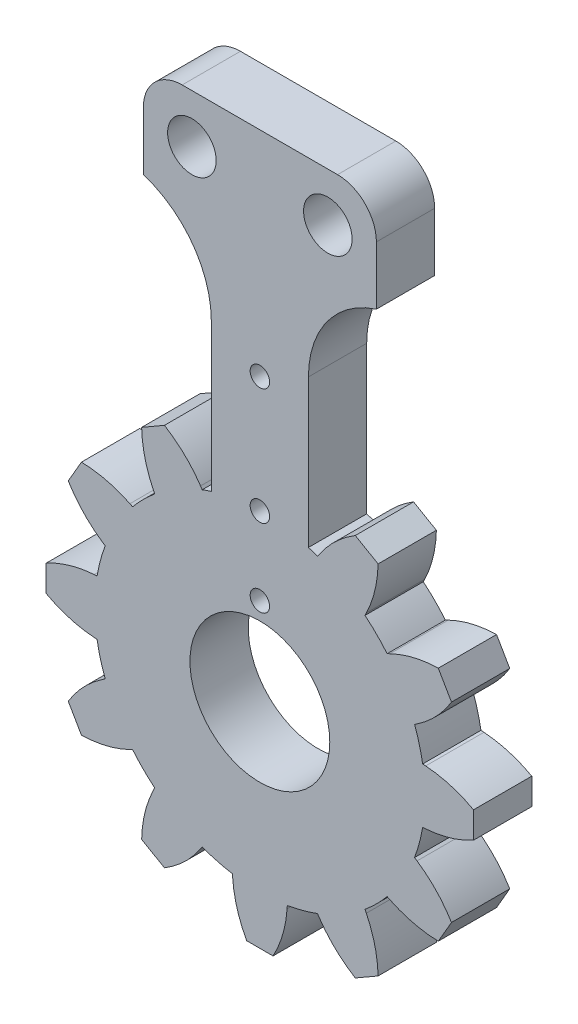
SolidWorks part; units mm, degrees
ref_plane "Front Plane" through (0, 0, 0) normal (0, 0, 1) x (1, 0, 0)
ref_plane "Top Plane" through (0, 0, 0) normal (0, 1, 0) x (1, 0, 0)
ref_plane "Right Plane" through (0, 0, 0) normal (1, 0, 0) x (0, 0, -1)
sketch "Sketch1" plane through (0, 0, 0) normal (0, 0, 1) x (1, 0, 0)
  circle A0 centre (0, 0) radius 8.5
  dimension "D1" = 17
extrude "Boss-Extrude1" add sketch "Sketch1" along normal blind 3
sketch "Sketch2" plane through (0, 0, 3) normal (0, 0, 1) x (1, 0, 0)
  line L0 (0, 0) -> (0, 10.5876) construction
  line L1 (0, 0) -> (1.4399, 10.9374) construction
  line L2 (0, 0) -> (-1.4446, 10.9725) construction
  circle A0 centre (0, 0) radius 10 construction
  dimension "D3" = 20
  dimension "D1" = 7.5
  dimension "D2" = 7.5
ref_point "Point3"
ref_point "Point4"
sketch "Sketch3" plane through (0, 0, 3) normal (0, 0, 1) x (1, 0, 0)
  line L0 (-1.3053, 9.9144) -> (-1.5091, 7)
  line L1 (-1.5091, 7) -> (1.5091, 7)
  line L2 (1.3053, 9.9144) -> (1.5091, 7)
  line L3 (1.3053, 9.9144) -> (0.6785, 11)
  line L4 (-1.3053, 9.9144) -> (-0.6785, 11)
  line L5 (-0.6785, 11) -> (0.6785, 11)
  dimension "D1" = 11
  dimension "D2" = 7
  dimension "D3" = 60
  dimension "D4" = 86
  dimension "D5" = 60
  dimension "D6" = 86
extrude "Boss-Extrude2" add sketch "Sketch3" against normal blind 3
pattern_circular "CirPattern2" count 12 over 360 about axis through (0, 0, 3) along (0, 0, -1) of "Boss-Extrude2"
fillet "Fillet5" radius 6 12 edges at (9.2388, 3.8268, 1.5) (6.0876, 7.9335, 1.5) (1.3053, 9.9144, 1.5) (-3.8268, 9.2388, 1.5) (-7.9335, 6.0876, 1.5) (-9.9144, 1.3053, 1.5) (-9.2388, -3.8268, 1.5) (-6.0876, -7.9335, 1.5) (-1.3053, -9.9144, 1.5) (3.8268, -9.2388, 1.5) (7.9335, -6.0876, 1.5) (9.9144, -1.3053, 1.5)
fillet "Fillet6" radius 6 12 edges at (7.9335, 6.0876, 1.5) (3.8268, 9.2388, 1.5) (-1.3053, 9.9144, 1.5) (-6.0876, 7.9335, 1.5) (-9.2388, 3.8268, 1.5) (-9.9144, -1.3053, 1.5) (-7.9335, -6.0876, 1.5) (-3.8268, -9.2388, 1.5) (1.3053, -9.9144, 1.5) (6.0876, -7.9335, 1.5) (9.2388, -3.8268, 1.5) (9.9144, 1.3053, 1.5)
sketch "Sketch4" plane through (0, 0, 0) normal (0, 0, -1) x (-1, 0, 0)
  line L0 (-2.5, 25.5) -> (-2.5, 4.3301)
  line L1 (-2.5, -4.3301) -> (-2.5, -7)
  line L2 (2.5, 4.3301) -> (2.5, 25.5)
  line L3 (2.5, 25.5) -> (-2.5, 25.5)
  line L4 (-2.5, -7) -> (2.5, -7)
  line L5 (2.5, -7) -> (2.5, -4.3301)
  arc A0 (-2.5, 4.3301) -> (-2.5, -4.3301) centre (0, 0) ccw
  arc A1 (2.5, -4.3301) -> (2.5, 4.3301) centre (0, 0) ccw
  dimension "D1" = 10
  dimension "D2" = 2.5
  dimension "D3" = 25.5
  dimension "D4" = 7
extrude "Boss-Extrude3" add sketch "Sketch4" against normal blind 3
sketch "Sketch18" plane through (0, 0, 0) normal (0, 0, 1) x (1, 0, 0)
  line L0 (0, 0) -> (-11, 0) construction
  line L1 (-11, 0.6785) -> (-11, -0.6785) construction
fillet "Fillet9" radius 2.5 2 edges at (-2.5, 25.5, 1.5) (2.5, 25.5, 1.5)
sketch "Sketch20" plane through (0, 0, 3) normal (0, 0, 1) x (1, 0, 0)
  line L0 (0, 0) -> (0, 25.5) construction
  circle A1 centre (0, 0) radius 3.6
  dimension "D1" = 7.2
extrude "Cut-Extrude11" cut sketch "Sketch20" against normal blind 10
sketch "Sketch21" plane through (0, 0, 3) normal (0, 0, 1) x (1, 0, 0)
  circle A0 centre (0, 14.5) radius 0.5
  circle A1 centre (0, 4.5) radius 0.5
  circle A2 centre (0, 8.5) radius 0.5
extrude "Cut-Extrude12" cut sketch "Sketch21" against normal blind 10
sketch "Sketch22" plane through (0, 0, 3) normal (0, 0, 1) x (1, 0, 0)
  line L0 (0, 25.5) -> (6, 25.5)
  line L1 (6, 25.5) -> (6, 20.5)
  line L2 (6, 20.5) -> (-6, 20.5)
  line L3 (-6, 20.5) -> (-6, 25.5)
  line L4 (-6, 25.5) -> (0, 25.5)
  dimension "D1" = 6
  dimension "D2" = 6
  dimension "D3" = 5
extrude "Boss-Extrude4" add sketch "Sketch22" against normal blind 3
sketch "Sketch23" plane through (0, 0, 3) normal (0, 0, 1) x (1, 0, 0)
  line L0 (6, 25.5) -> (-6, 25.5) construction
  line L1 (6, 25.5) -> (-6, 25.5) construction
  line L2 (-6, 25.5) -> (-6, 20.5) construction
  line L3 (6, 20.5) -> (6, 25.5) construction
  circle A0 centre (-3.5, 23) radius 1.25
  circle A1 centre (3.5, 23) radius 1.25
  dimension "D5" = 2.5
  dimension "D6" = 2.5
  dimension "D1" = 2.5
  dimension "D2" = 2.5
  dimension "D3" = 2.5
  dimension "D4" = 2.5
extrude "Cut-Extrude13" cut sketch "Sketch23" against normal blind 3
fillet "Fillet10" radius 5 2 edges at (2.5, 20.5, 1.5) (-2.5, 20.5, 1.5)
fillet "Fillet11" radius 2 2 edges at (-6, 25.5, 1.5) (6, 25.5, 1.5)
